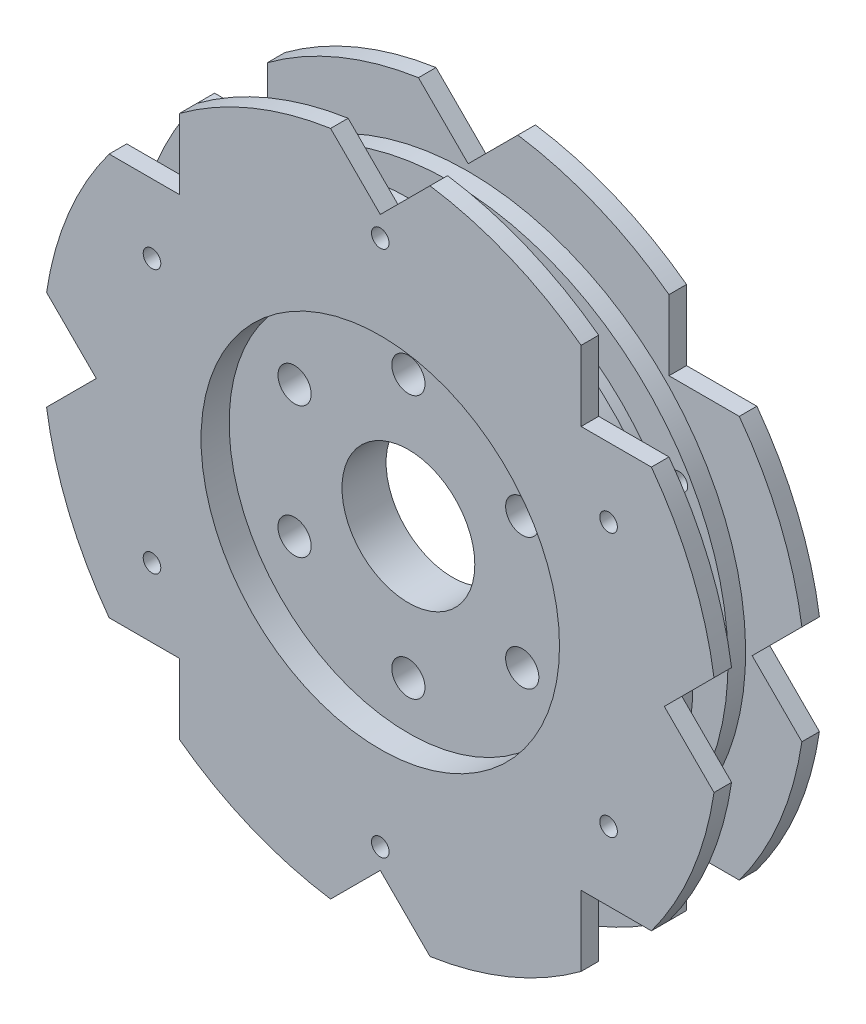
SolidWorks part; units mm, degrees
material "PE High Density Film"
ref_plane "Front Plane" through (0, 0, 0) normal (0, 0, 1) x (1, 0, 0)
ref_plane "Top Plane" through (0, 0, 0) normal (0, 1, 0) x (1, 0, 0)
ref_plane "Right Plane" through (0, 0, 0) normal (1, 0, 0) x (0, 0, -1)
sketch "Sketch1" plane through (0, 0, 0) normal (0, 0, 1) x (1, 0, 0)
  line L0 (0, 0) -> (0, 60.96) construction
  line L1 (-8.9803, 60.2949) -> (0, 51.3147)
  line L2 (0, 51.3147) -> (8.9803, 60.2949)
  line L3 (36.2849, 48.9849) -> (36.2849, 36.2849)
  line L4 (36.2849, 36.2849) -> (48.9849, 36.2849)
  line L5 (60.2949, 8.9803) -> (51.3147, 0)
  line L6 (51.3147, 0) -> (60.2949, -8.9803)
  line L7 (48.9849, -36.2849) -> (36.2849, -36.2849)
  line L8 (36.2849, -36.2849) -> (36.2849, -48.9849)
  line L9 (8.9803, -60.2949) -> (0, -51.3147)
  line L10 (0, -51.3147) -> (-8.9803, -60.2949)
  line L11 (-36.2849, -48.9849) -> (-36.2849, -36.2849)
  line L12 (-36.2849, -36.2849) -> (-48.9849, -36.2849)
  line L13 (-60.2949, -8.9803) -> (-51.3147, 0)
  line L14 (-51.3147, 0) -> (-60.2949, 8.9803)
  line L15 (-48.9849, 36.2849) -> (-36.2849, 36.2849)
  line L16 (-36.2849, 36.2849) -> (-36.2849, 48.9849)
  arc A0 (-60.2949, -8.9803) -> (-48.9849, -36.2849) centre (0, 0) ccw
  arc A1 (-48.9849, 36.2849) -> (-60.2949, 8.9803) centre (0, 0) ccw
  arc A2 (-36.2849, -48.9849) -> (-8.9803, -60.2949) centre (0, 0) ccw
  arc A3 (8.9803, -60.2949) -> (36.2849, -48.9849) centre (0, 0) ccw
  arc A4 (48.9849, -36.2849) -> (60.2949, -8.9803) centre (0, 0) ccw
  arc A5 (60.2949, 8.9803) -> (48.9849, 36.2849) centre (0, 0) ccw
  arc A6 (36.2849, 48.9849) -> (8.9803, 60.2949) centre (0, 0) ccw
  arc A7 (-8.9803, 60.2949) -> (-36.2849, 48.9849) centre (0, 0) ccw
  point P30 (0, 0)
  dimension "D1" = 121.92
  dimension "D2" = 45
  dimension "D3" = 12.7
  dimension "D4" = 8
extrude "Boss-Extrude1" add sketch "Sketch1" along normal blind 19.05
sketch "Sketch2" plane through (0, 0, 19.05) normal (0, 0, 1) x (1, 0, 0)
  circle A0 centre (0, 0) radius 12
  dimension "D1" = 24
extrude "Cut-Extrude1" cut sketch "Sketch2" against normal through all contours A0 region at (0, 0, 19.05)
sketch "Sketch3" plane through (0, 0, 19.05) normal (0, 0, 1) x (1, 0, 0)
  circle A0 centre (0, 0) radius 32.385
  dimension "D1" = 64.77
extrude "Cut-Extrude2" cut sketch "Sketch3" against normal blind 5.08
sketch "Sketch4" plane through (0, 0, 0) normal (0, 0, -1) x (-1, 0, 0)
  circle A0 centre (0, 0) radius 28.4
  dimension "D1" = 56.8
extrude "Cut-Extrude3" cut sketch "Sketch4" against normal blind 6
sketch "Sketch5" plane through (0, 0, 6) normal (0, 0, -1) x (-1, 0, 0)
  line L0 (0, 0) -> (0, 23.75) construction
  circle A0 centre (0, 0) radius 23.75 construction
  circle A1 centre (0, 23.75) radius 2.6
  circle A2 centre (20.5681, 11.875) radius 2.6
  circle A3 centre (20.5681, -11.875) radius 2.6
  circle A4 centre (0, -23.75) radius 2.6
  circle A5 centre (-20.5681, -11.875) radius 2.6
  circle A6 centre (-20.5681, 11.875) radius 2.6
  point P17 (0, 0)
  dimension "D1" = 47.5
  dimension "D2" = 5.2
  dimension "D3" = 6
hole_wizard "Ø6.0mm Dowel Hole1" positions "Sketch6" profile "Sketch8" hole size "Ø6.0" standard "ANSI Metric" end condition through all
sketch "Sketch6" plane through (0, 0, 6) normal (0, 0, -1) x (-1, 0, 0)
  point P0 (0, 23.75)
  point P3 (20.5681, 11.875)
  point P6 (20.5681, -11.875)
  point P9 (0, -23.75)
  point P13 (-20.5681, 11.875)
  point P16 (-20.5681, -11.875)
sketch "Sketch8" plane through (0, 23.75, 6) normal (1, 0, 0) x (0, 1, 0)
  line L0 (0, 0) -> (0, 13.05)
  line L1 (0, 13.05) -> (3, 13.05)
  line L2 (3, 13.05) -> (3, 0)
  line L5 (3, 0) -> (0, 0)
  line L11 (0, -6.35) -> (0, 107.95) construction
  dimension "Thru Hole Dia." = 6
  dimension "Thru Hole Depth" = 13.05
ref_plane "Plane1" through (0, 0, 9.525) normal (0, 0, -1) x (-1, 0, 0)
sketch "Sketch9" plane through (0, 0, 9.525) normal (0, 0, -1) x (-1, 0, 0)
  line L0 (0, 0) -> (23.3284, 56.3197) construction
  line L1 (20.2908, 48.9864) -> (11.4909, 52.6315) construction
  line L2 (17.2533, 41.6531) -> (8.4533, 45.2982)
  line L3 (8.4533, 45.2982) -> (14.5284, 59.9648)
  line L4 (14.5284, 59.9648) -> (32.1283, 52.6746)
  line L5 (32.1283, 52.6746) -> (26.0532, 38.008)
  line L6 (26.0532, 38.008) -> (17.2533, 41.6531)
  arc A0 (36.2849, 48.9849) -> (8.9803, 60.2949) centre (0, 0) ccw construction
  circle A1 centre (20.2908, 48.9864) radius 3.4925
  dimension "D1" = 6.985
  dimension "D2" = 7.9375
  dimension "D3" = 19.05
extrude "Cut-Extrude4" [suppressed] cut sketch "Sketch9" against normal mid plane 11.1125
sketch "Sketch10" [suppressed] plane through (0, 0, 0) normal (0, 0, -1) x (-1, 0, 0)
  circle A0 centre (20.2908, 48.9864) radius 3.4925
  circle A1 centre (20.2908, 48.9864) radius 3.4925 construction
extrude "Cut-Extrude5" [suppressed] cut sketch "Sketch10" against normal through all
sketch "Sketch11" plane through (0, 0, 9.525) normal (0, 0, -1) x (-1, 0, 0)
  line L0 (0, 0) -> (0, 50.8) construction
  line L1 (0, 38.1) -> (-15.875, 38.1)
  line L2 (-15.875, 38.1) -> (-15.875, 63.5)
  line L3 (-15.875, 63.5) -> (15.875, 63.5)
  line L4 (15.875, 63.5) -> (15.875, 38.1)
  line L5 (15.875, 38.1) -> (0, 38.1)
  line L6 (0, 50.8) -> (-15.875, 50.8) construction
  line L7 (0, 0) -> (25.4, 0) construction
  dimension "D1" = 25.4
  dimension "D2" = 90
  dimension "D3" = 31.75
  dimension "D4" = 25.4
  dimension "D5" = 50.8
extrude "Cut-Extrude6" [suppressed] cut sketch "Sketch11" against normal mid plane 11.1125
sketch "Sketch12" plane through (0, 0, 0) normal (1, 0, 0) x (0, 0, -1)
  line L0 (0, 0) -> (-19.05, 0) construction
  line L1 (-9.525, 0) -> (-9.525, 60.2949) construction
  line L2 (-19.05, 60.2949) -> (0, 60.2949) construction
  line L3 (-3.175, 62.8349) -> (-15.875, 62.8349)
  line L4 (-15.875, 62.8349) -> (-15.875, 50.1349)
  line L5 (-15.875, 50.1349) -> (-12.7, 50.1349)
  line L6 (-12.7, 50.1349) -> (-12.7, 43.7849)
  line L7 (-12.7, 43.7849) -> (-6.35, 43.7849)
  line L8 (-6.35, 43.7849) -> (-6.35, 50.1349)
  line L9 (-6.35, 50.1349) -> (-3.175, 50.1349)
  line L10 (-3.175, 50.1349) -> (-3.175, 62.8349)
  point P10 (0, 0)
  point P17 (-26.7255, 62.8349)
  point P18 (-9.525, 62.8349)
  point P19 (-9.525, 43.7849)
  dimension "D1" = 2.54
  dimension "D2" = 12.7
  dimension "D3" = 12.7
  dimension "D4" = 6.35
  dimension "D5" = 6.35
revolve "Cut-Revolve1" cut sketch "Sketch12" angle 360 about L0
sketch "Sketch13" plane through (0, 0, 0) normal (0, 0, -1) x (-1, 0, 0)
  circle A0 centre (0, 47.625) radius 1.5875
  circle A1 centre (41.2445, 23.8125) radius 1.5875
  circle A2 centre (41.2445, -23.8125) radius 1.5875
  circle A3 centre (0, -47.625) radius 1.5875
  circle A4 centre (-41.2445, -23.8125) radius 1.5875
  circle A5 centre (-41.2445, 23.8125) radius 1.5875
  circle A6 centre (0, 0) radius 47.625
  point P4 (0, 0)
  point P15 (0, 0)
  point P17 (-41.8911, -14.864)
  point P18 (0, 0)
  dimension "D1" = 3.175
  dimension "D3" = 95.25
  dimension "D2" = 6
hole_wizard "1/8 (0.1250) Dowel Hole1" positions "Sketch14" profile "Sketch15" hole size "1/8" standard "ANSI Inch" end condition through all
sketch "Sketch14" plane through (0, 0, 0) normal (0, 0, -1) x (-1, 0, 0)
  point P0 (-41.2445, 23.8125)
  point P3 (0, 47.625)
  point P6 (41.2445, 23.8125)
  point P9 (41.2445, -23.8125)
  point P12 (0, -47.625)
  point P15 (-41.2445, -23.8125)
sketch "Sketch15" plane through (41.2445, 23.8125, 0) normal (1, 0, 0) x (0, 1, 0)
  line L0 (0, 0) -> (0, 19.05)
  line L1 (0, 19.05) -> (1.5875, 19.05)
  line L2 (1.5875, 19.05) -> (1.5875, 0)
  line L5 (1.5875, 0) -> (0, 0)
  line L11 (0, -6.35) -> (0, 107.95) construction
  dimension "Thru Hole Dia." = 3.175
  dimension "Thru Hole Depth" = 19.05
equation "\"D2@Sketch9\"=0.3125"
